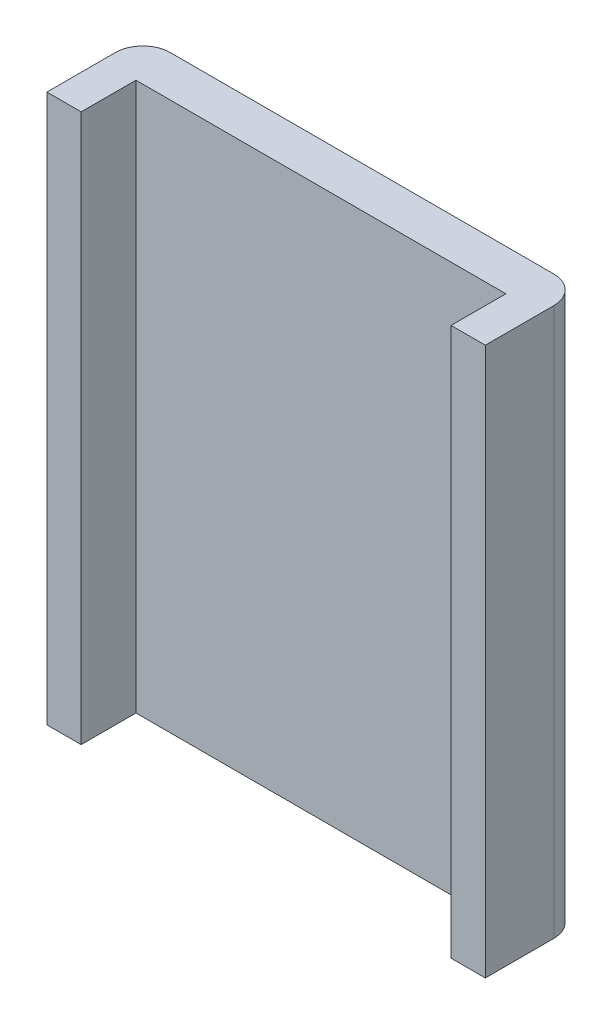
SolidWorks part; units mm, degrees
ref_plane "Front Plane" through (0, 0, 0) normal (0, 0, 1) x (1, 0, 0)
ref_plane "Top Plane" through (0, 0, 0) normal (0, 1, 0) x (1, 0, 0)
ref_plane "Right Plane" through (0, 0, 0) normal (1, 0, 0) x (0, 0, -1)
sketch "Sketch1" plane through (0, 0, 0) normal (0, 0, 1) x (1, 0, 0)
  line L1 (-4, 5) -> (4, 5)
  line L2 (-4, 5) -> (-4, -5)
  line L3 (-4, -5) -> (4, -5)
  line L4 (4, 5) -> (4, -5)
  line L5 (-4, 5) -> (4, -5) construction
  line L6 (-4, -5) -> (4, 5) construction
  line L7 (-3.375, 5) -> (3.375, 5)
  line L8 (-3.375, 5) -> (-3.375, -5)
  line L9 (-3.375, -5) -> (3.375, -5)
  line L10 (3.375, 5) -> (3.375, -5)
  line L11 (-3.375, 5) -> (3.375, -5) construction
  line L12 (-3.375, -5) -> (3.375, 5) construction
  point P0 (0, 0)
  point P6 (0, 0)
  dimension "D1" = 8
  dimension "D2" = 10
  dimension "D3" = 10
  dimension "D4" = 6.75
extrude "Boss-Extrude1" add sketch "Sketch1" along normal blind 0.75 contours L10 L1 L8 L3 region at (0, 0, 0)
extrude "Boss-Extrude2" add sketch "Sketch1<3>" along normal blind 1.75 contours L1 L10 L3 L4 | L8 L1 L2 L3 region at (-3.6875, 0, 0) region at (3.6875, 0, 0)
sketch "Sketch1<3>" plane through (0, 0, 0) normal (0, 0, 1) x (1, 0, 0) same geometry as "Sketch1"
ref_axis "Axis1" through (0, 0, -4.7229) along (0, 0, 1)
ref_plane "Plane1" through (0, 0, 0) normal (0.9659, 0.2588, 0) x (0, 0, 1)
ref_plane "Plane2" through (0, 0, 0) normal (0.9659, -0.2588, 0) x (0, 0, 1)
fillet "Fillet1" radius 0.5 2 edges at (-4, 0, 0) (4, 0, 0)
equation "\"D3@Sketch1\"=\"D2@Sketch1\""
